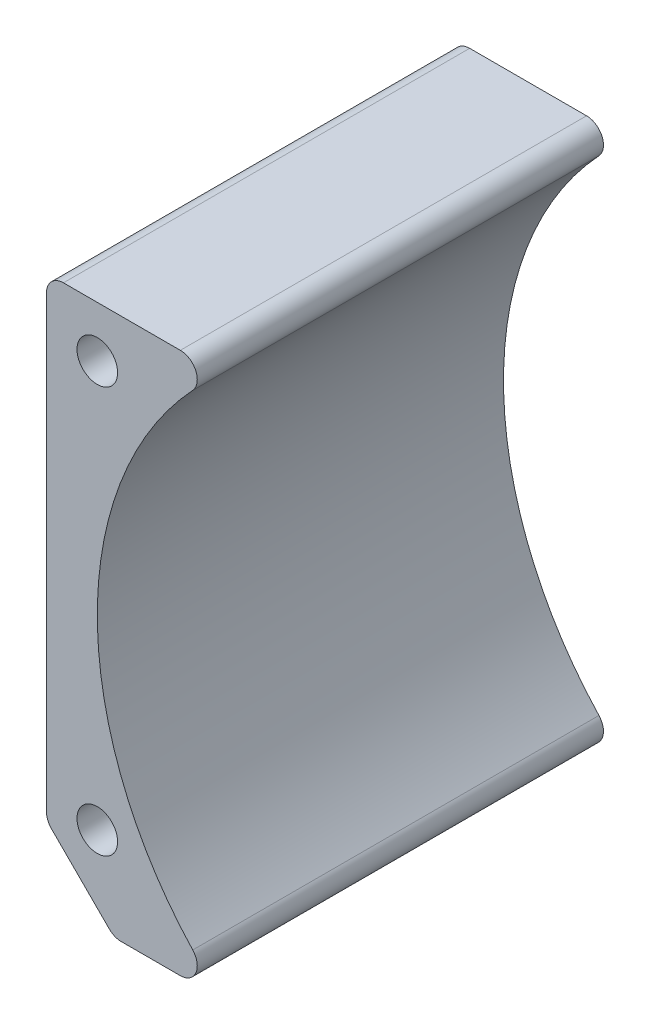
SolidWorks part; units mm, degrees
ref_plane "Front Plane" through (0, 0, 0) normal (0, 0, 1) x (1, 0, 0)
ref_plane "Top Plane" through (0, 0, 0) normal (0, 1, 0) x (1, 0, 0)
ref_plane "Right Plane" through (0, 0, 0) normal (1, 0, 0) x (0, 0, -1)
sketch "Sketch1" plane through (0, 0, 0) normal (0, 0, 1) x (1, 0, 0)
  line L1 (0, 0) -> (16.5077, 0)
  line L2 (0, 0) -> (0, 50.8)
  line L3 (0, 50.8) -> (16.5077, 50.8)
  arc A0 (16.5077, 50.8) -> (16.5077, 0) centre (38.1, 25.4) ccw
  dimension "D4" = 66.675
  dimension "D1" = 50.8
  dimension "D2" = 25.4
  dimension "D3" = 38.1
extrude "Boss-Extrude1" add sketch "Sketch1" along normal blind 38.1
sketch "Sketch2" plane through (0, 0, 38.1) normal (0, 0, 1) x (1, 0, 0)
  line L0 (16.5077, 50.8) -> (0, 50.8) construction
  line L1 (0, 50.8) -> (0, 0) construction
  line L2 (0, 0) -> (16.5077, 0) construction
  circle A0 centre (4.7625, 46.0375) radius 1.905
  circle A1 centre (4.7625, 7.9375) radius 1.905
  dimension "D4" = 3.81
  dimension "D1" = 4.7625
  dimension "D2" = 4.7625
  dimension "D3" = 7.9375
extrude "Cut-Extrude1" cut sketch "Sketch2" against normal through all
chamfer "Chamfer1" distance 6.35 angle 45 1 edges at (0, 0, 19.05)
fillet "Fillet1" radius 1.5875 5 edges at (0, 6.35, 19.05) (6.35, 0, 19.05) (16.5077, 0, 19.05) (16.5077, 50.8, 19.05) (0, 50.8, 19.05)
